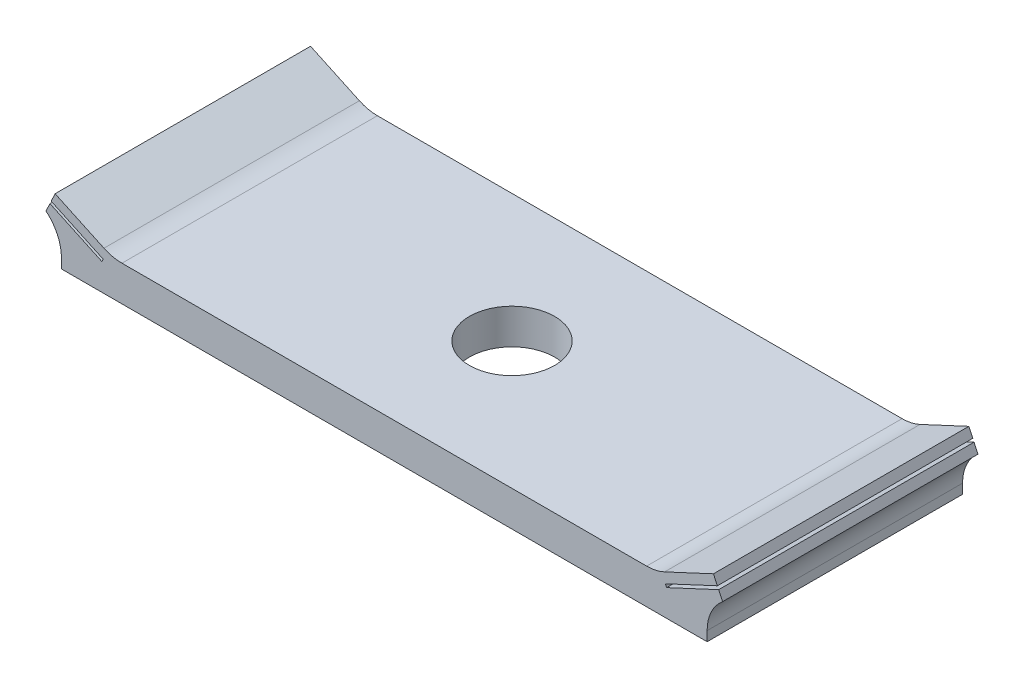
SolidWorks part; units mm, degrees
ref_plane "Front Plane" through (0, 0, 0) normal (0, 0, 1) x (1, 0, 0)
ref_plane "Top Plane" through (0, 0, 0) normal (0, 1, 0) x (1, 0, 0)
ref_plane "Right Plane" through (0, 0, 0) normal (1, 0, 0) x (0, 0, -1)
sketch "Sketch1" plane through (0, 0, 0) normal (0, 0, 1) x (1, 0, 0)
  line L0 (37.92, 2.0705) -> (39.7326, 2.9157)
  line L1 (-37.92, -2.0705) -> (37.92, -2.0705)
  line L2 (-37.92, -2.0705) -> (-37.92, 2.0705)
  line L3 (-37.92, 2.0705) -> (37.92, 2.0705)
  line L4 (37.92, -2.0705) -> (37.92, 2.0705)
  line L5 (-37.92, -2.0705) -> (37.92, 2.0705) construction
  line L6 (-37.92, 2.0705) -> (37.92, -2.0705) construction
  line L7 (39.7326, 2.9157) -> (38.661, 5.2139)
  line L8 (38.661, 5.2139) -> (31.92, 2.0705)
  line L9 (39.1228, 4.2234) -> (33.0143, 1.375)
  line L10 (33.0143, 1.375) -> (33.1622, 1.0578)
  line L11 (33.1622, 1.0578) -> (39.2708, 3.9062)
  line L12 (0, 0) -> (0, -50000) construction
  line L13 (-37.92, 2.0705) -> (-39.7326, 2.9157)
  line L14 (-33.0143, 1.375) -> (-33.1622, 1.0578)
  line L15 (-33.1622, 1.0578) -> (-39.2708, 3.9062)
  line L16 (-39.1228, 4.2234) -> (-33.0143, 1.375)
  line L17 (-39.7326, 2.9157) -> (-38.661, 5.2139)
  line L18 (-38.661, 5.2139) -> (-31.92, 2.0705)
  line L19 (36.368, 2.7457) -> (45351.7574, 21133.6588) construction
  point P0 (0, 0)
  point P25 (33.0883, 1.2164)
  point P26 (39.1968, 4.0648)
  dimension "D1" = 25
  dimension "D2" = 31.92
  dimension "D5" = 37.92
  dimension "D6" = 2
  dimension "D7" = 0.35
  dimension "D9" = 6.74
extrude "Boss-Extrude1" add sketch "Sketch1" along normal blind 30 contours L3 L16 L14 L15 L2 L1 L4 L11 L10 L9 | L17 L13 L3 L15 | L18 L17 L16 L3 | L9 L7 L8 L3 | L11 L3 L0 L7 region at (37.9705, 2.7712, 0) region at (0, -0.0074, 0) region at (36.0049, 3.41, 0) region at (-37.9705, 2.7712, 0) region at (-36.0049, 3.41, 0)
fillet "Fillet1" radius 5 4 edges at (37.92, 2.0705, 15) (-37.92, 2.0705, 15) (31.92, 2.0705, 15) (-31.92, 2.0705, 15)
sketch "Sketch2" plane through (0, 2.0705, 0) normal (0, 1, 0) x (1, 0, 0)
  line L0 (-30.8115, 0) -> (30.8115, 0) construction
  circle A0 centre (0, -15) radius 5
  dimension "D1" = 10
  dimension "D2" = 15
extrude "Cut-Extrude1" cut sketch "Sketch2" against normal blind 30
